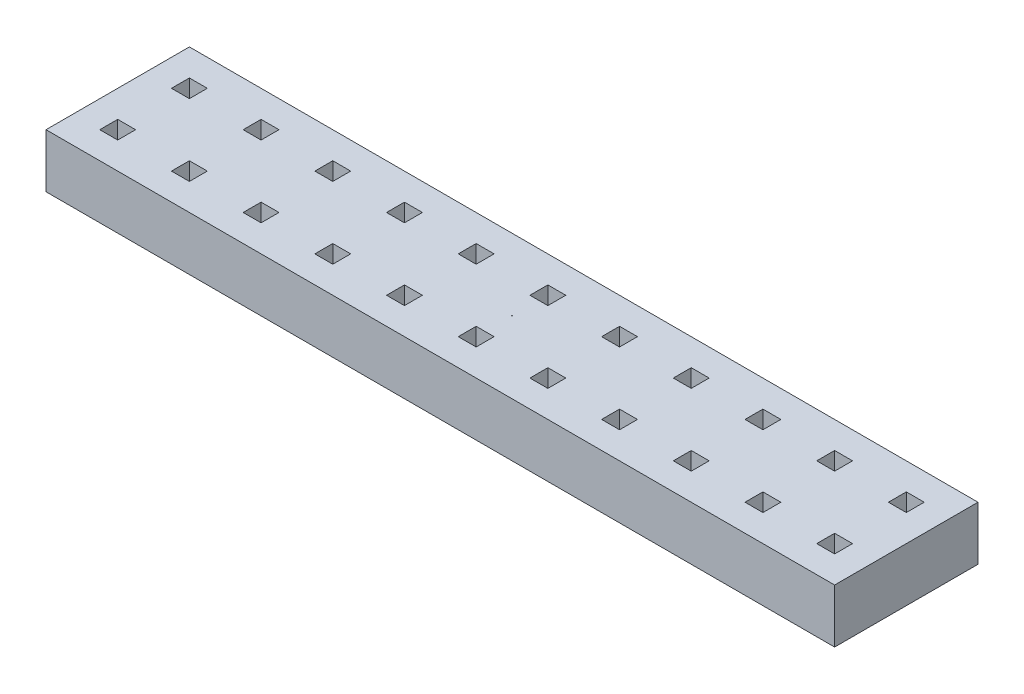
SolidWorks part; units mm, degrees
ref_plane "Front Plane" through (0, 0, 0) normal (0, 0, 1) x (1, 0, 0)
ref_plane "Top Plane" through (0, 0, 0) normal (0, 1, 0) x (1, 0, 0)
ref_plane "Right Plane" through (0, 0, 0) normal (1, 0, 0) x (0, 0, -1)
sketch "Sketch1" plane through (0, 0, 0) normal (0, 1, 0) x (1, 0, 0)
  line L1 (0, 0) -> (22, 0)
  line L2 (0, 0) -> (0, 4)
  line L3 (0, 4) -> (22, 4)
  line L4 (22, 0) -> (22, 4)
extrude "Boss-Extrude1" add sketch "Sketch1" along normal blind 1.5
sketch "Sketch2" plane through (0, 1.5, 0) normal (0, 1, 0) x (1, 0, 0)
  line L0 (2.75, 3.25) -> (2.75, 2.75)
  line L1 (0.75, 3.25) -> (1.25, 3.25)
  line L2 (0.75, 3.25) -> (0.75, 2.75)
  line L3 (0.75, 2.75) -> (1.25, 2.75)
  line L4 (1.25, 3.25) -> (1.25, 2.75)
  line L5 (2.75, 3.25) -> (3.25, 3.25)
  line L6 (3.25, 3.25) -> (3.25, 2.75)
  line L7 (2.75, 2.75) -> (3.25, 2.75)
  line L8 (4.75, 3.25) -> (4.75, 2.75)
  line L9 (4.75, 3.25) -> (5.25, 3.25)
  line L10 (5.25, 3.25) -> (5.25, 2.75)
  line L11 (4.75, 2.75) -> (5.25, 2.75)
  line L12 (6.75, 3.25) -> (6.75, 2.75)
  line L13 (6.75, 3.25) -> (7.25, 3.25)
  line L14 (7.25, 3.25) -> (7.25, 2.75)
  line L15 (6.75, 2.75) -> (7.25, 2.75)
  line L16 (8.75, 3.25) -> (8.75, 2.75)
  line L17 (8.75, 3.25) -> (9.25, 3.25)
  line L18 (9.25, 3.25) -> (9.25, 2.75)
  line L19 (8.75, 2.75) -> (9.25, 2.75)
  line L20 (10.75, 3.25) -> (10.75, 2.75)
  line L21 (10.75, 3.25) -> (11.25, 3.25)
  line L22 (11.25, 3.25) -> (11.25, 2.75)
  line L23 (10.75, 2.75) -> (11.25, 2.75)
  line L24 (12.75, 3.25) -> (12.75, 2.75)
  line L25 (12.75, 3.25) -> (13.25, 3.25)
  line L26 (13.25, 3.25) -> (13.25, 2.75)
  line L27 (12.75, 2.75) -> (13.25, 2.75)
  line L28 (14.75, 3.25) -> (14.75, 2.75)
  line L29 (14.75, 3.25) -> (15.25, 3.25)
  line L30 (15.25, 3.25) -> (15.25, 2.75)
  line L31 (14.75, 2.75) -> (15.25, 2.75)
  line L32 (16.75, 3.25) -> (16.75, 2.75)
  line L33 (16.75, 3.25) -> (17.25, 3.25)
  line L34 (17.25, 3.25) -> (17.25, 2.75)
  line L35 (16.75, 2.75) -> (17.25, 2.75)
  line L36 (18.75, 3.25) -> (18.75, 2.75)
  line L37 (18.75, 3.25) -> (19.25, 3.25)
  line L38 (19.25, 3.25) -> (19.25, 2.75)
  line L39 (18.75, 2.75) -> (19.25, 2.75)
  line L40 (20.75, 3.25) -> (20.75, 2.75)
  line L41 (20.75, 3.25) -> (21.25, 3.25)
  line L42 (21.25, 3.25) -> (21.25, 2.75)
  line L43 (20.75, 2.75) -> (21.25, 2.75)
  line L72 (0.75, 1.25) -> (0.75, 0.75)
  line L73 (0.75, 1.25) -> (1.25, 1.25)
  line L74 (1.25, 1.25) -> (1.25, 0.75)
  line L75 (0.75, 0.75) -> (1.25, 0.75)
  line L76 (2.75, 1.25) -> (2.75, 0.75)
  line L77 (2.75, 1.25) -> (3.25, 1.25)
  line L78 (3.25, 1.25) -> (3.25, 0.75)
  line L79 (2.75, 0.75) -> (3.25, 0.75)
  line L80 (4.75, 1.25) -> (4.75, 0.75)
  line L81 (4.75, 1.25) -> (5.25, 1.25)
  line L82 (5.25, 1.25) -> (5.25, 0.75)
  line L83 (4.75, 0.75) -> (5.25, 0.75)
  line L84 (6.75, 1.25) -> (6.75, 0.75)
  line L85 (6.75, 1.25) -> (7.25, 1.25)
  line L86 (7.25, 1.25) -> (7.25, 0.75)
  line L87 (6.75, 0.75) -> (7.25, 0.75)
  line L88 (8.75, 1.25) -> (8.75, 0.75)
  line L89 (8.75, 1.25) -> (9.25, 1.25)
  line L90 (9.25, 1.25) -> (9.25, 0.75)
  line L91 (8.75, 0.75) -> (9.25, 0.75)
  line L92 (10.75, 1.25) -> (10.75, 0.75)
  line L93 (10.75, 1.25) -> (11.25, 1.25)
  line L94 (11.25, 1.25) -> (11.25, 0.75)
  line L95 (10.75, 0.75) -> (11.25, 0.75)
  line L96 (12.75, 1.25) -> (12.75, 0.75)
  line L97 (12.75, 1.25) -> (13.25, 1.25)
  line L98 (13.25, 1.25) -> (13.25, 0.75)
  line L99 (12.75, 0.75) -> (13.25, 0.75)
  line L100 (14.75, 1.25) -> (14.75, 0.75)
  line L101 (14.75, 1.25) -> (15.25, 1.25)
  line L102 (15.25, 1.25) -> (15.25, 0.75)
  line L103 (14.75, 0.75) -> (15.25, 0.75)
  line L104 (16.75, 1.25) -> (16.75, 0.75)
  line L105 (16.75, 1.25) -> (17.25, 1.25)
  line L106 (17.25, 1.25) -> (17.25, 0.75)
  line L107 (16.75, 0.75) -> (17.25, 0.75)
  line L108 (18.75, 1.25) -> (18.75, 0.75)
  line L109 (18.75, 1.25) -> (19.25, 1.25)
  line L110 (19.25, 1.25) -> (19.25, 0.75)
  line L111 (18.75, 0.75) -> (19.25, 0.75)
  line L112 (20.75, 1.25) -> (20.75, 0.75)
  line L113 (20.75, 1.25) -> (21.25, 1.25)
  line L114 (21.25, 1.25) -> (21.25, 0.75)
  line L115 (20.75, 0.75) -> (21.25, 0.75)
  dimension "D1" = 11
  dimension "D2" = 2
extrude "Cut-Extrude1" cut sketch "Sketch2" against normal blind 2
sketch "Sketch3" plane through (0, 1.5, 0) normal (0, 1, 0) x (1, 0, 0)
  circle A0 centre (11, 2) radius 0.01
  point P0 (11, 2)
ref_axis "Axis1" [suppressed] through (11, -5.3844, -2) along (0, 1, 0)
extrude "Cut-Extrude2" cut sketch "Sketch3" against normal blind 1.5
ref_plane "Plane1" through (2.431, 0, -5.6724) normal (-0.3939, 0, 0.9191) x (0.9191, 0, 0.3939)
ref_plane "Plane2" through (0.9828, 0, 2.2931) normal (-0.3939, 0, -0.9191) x (-0.9191, 0, 0.3939)
ref_axis "Axis2" through (11, -0.075, -2) along (0, 1, 0)
